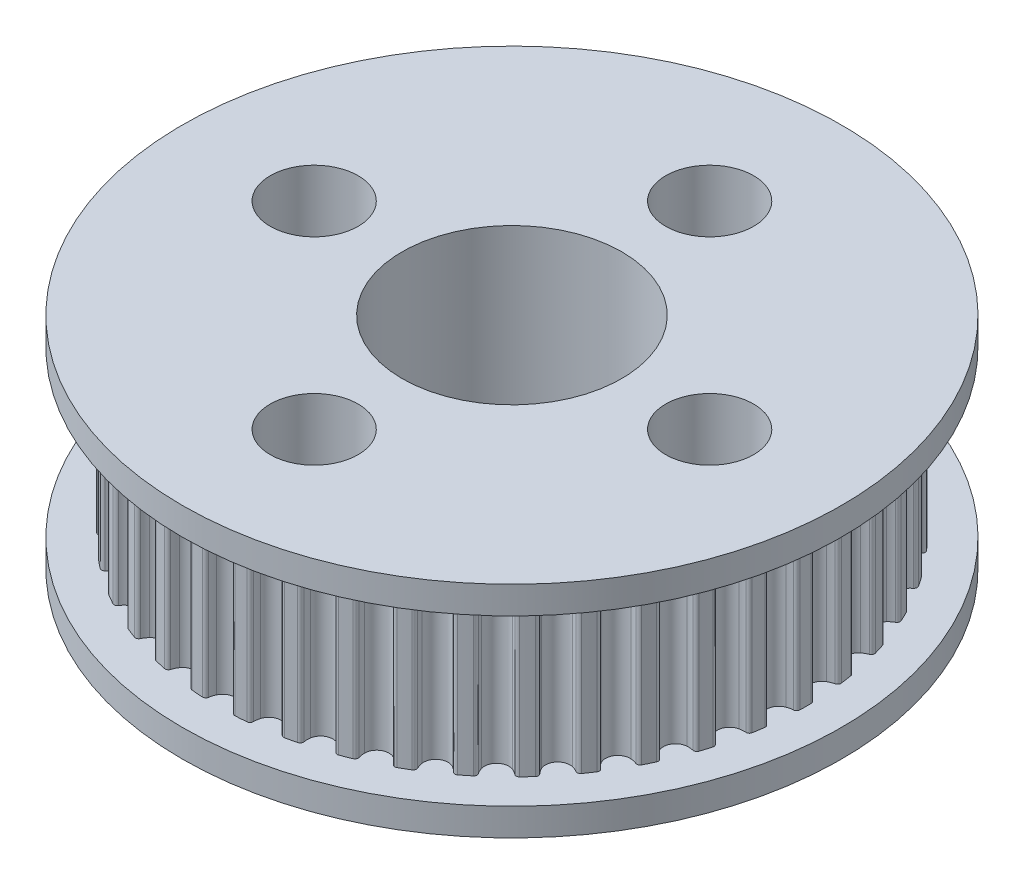
SolidWorks part; units mm, degrees
ref_plane "Front Plane" through (0, 0, 0) normal (0, 0, 1) x (1, 0, 0)
ref_plane "Top Plane" through (0, 0, 0) normal (0, 1, 0) x (1, 0, 0)
ref_plane "Right Plane" through (0, 0, 0) normal (1, 0, 0) x (0, 0, -1)
sketch "Sketch2" plane through (0, 0, 0) normal (0, 1, 0) x (1, 0, 0)
  arc A0 (-0.7447, 13.3442) -> (0.7447, 13.3442) centre (0, 0) ccw
  arc A1 (-0.5031, 12.9334) -> (0.5031, 12.9334) centre (0, 13.17) ccw
  arc A2 (0.5031, 12.9334) -> (0.5879, 13.2159) centre (-0.4018, 13.359) ccw
  arc A3 (-0.5879, 13.2159) -> (-0.5031, 12.9334) centre (0.4018, 13.359) ccw
  arc A4 (-0.7447, 13.3442) -> (-0.5879, 13.2159) centre (-0.7364, 13.1945) cw
  arc A5 (0.7447, 13.3442) -> (0.5879, 13.2159) centre (0.7364, 13.1945) ccw
  arc A6 (1.2524, 13.3062) -> (1.3884, 13.1559) centre (1.2384, 13.1568) cw
  arc A7 (1.3884, 13.1559) -> (1.4301, 12.8639) centre (2.3883, 13.1499) ccw
  arc A8 (1.4301, 12.8639) -> (2.4251, 12.7139) centre (1.9629, 13.0229) ccw
  arc A9 (2.4251, 12.7139) -> (2.5511, 12.9807) centre (1.5938, 13.2696) ccw
  arc A10 (2.7253, 13.0842) -> (2.5511, 12.9807) centre (2.6947, 12.9373) ccw
  arc A11 (3.2216, 12.9709) -> (3.3336, 12.8021) centre (3.1855, 12.8253) cw
  arc A12 (3.3336, 12.8021) -> (3.3314, 12.5071) centre (4.3216, 12.647) ccw
  arc A13 (3.3314, 12.5071) -> (4.293, 12.2105) centre (3.8819, 12.5849) ccw
  arc A14 (4.293, 12.2105) -> (4.4573, 12.4555) centre (3.5537, 12.8839) ccw
  arc A15 (4.6449, 12.5319) -> (4.4573, 12.4555) centre (4.5928, 12.3912) ccw
  arc A16 (5.1188, 12.3459) -> (5.2045, 12.1622) centre (5.0614, 12.2073) cw
  arc A17 (5.2045, 12.1622) -> (5.1583, 11.8709) centre (6.1582, 11.8617) ccw
  arc A18 (5.1583, 11.8709) -> (6.0649, 11.4343) centre (5.7142, 11.8658) ccw
  arc A19 (6.0649, 11.4343) -> (6.2639, 11.652) centre (5.4342, 12.2103) ccw
  arc A20 (6.4608, 11.6996) -> (6.2639, 11.652) centre (6.3883, 11.5683) ccw
  arc A21 (6.9017, 11.4451) -> (6.959, 11.2507) centre (6.8243, 11.3166) cw
  arc A22 (6.959, 11.2507) -> (6.8699, 10.9695) centre (7.8573, 10.8114) ccw
  arc A23 (6.8699, 10.9695) -> (7.7013, 10.4026) centre (7.4189, 10.8816) ccw
  arc A24 (7.7013, 10.4026) -> (7.9306, 10.5883) centre (7.1934, 11.264) ccw
  arc A25 (8.1324, 10.606) -> (7.9306, 10.5883) centre (8.0411, 10.487) ccw
  arc A26 (8.5304, 10.2886) -> (8.5581, 10.0879) centre (8.4347, 10.1731) cw
  arc A27 (8.5581, 10.0879) -> (8.4281, 9.8231) centre (9.3809, 9.5195) ccw
  arc A28 (8.4281, 9.8231) -> (9.1658, 9.1386) centre (8.9579, 9.6543) ccw
  arc A29 (9.1658, 9.1386) -> (9.4201, 9.2881) centre (8.7919, 10.0661) ccw
  arc A30 (9.6223, 9.2755) -> (9.4201, 9.2881) centre (9.5143, 9.1714) ccw
  arc A31 (9.9686, 8.9023) -> (9.9661, 8.6997) centre (9.8567, 8.8023) cw
  arc A32 (9.9661, 8.6997) -> (9.798, 8.4572) centre (10.695, 8.015) ccw
  arc A33 (9.798, 8.4572) -> (10.4254, 7.6705) centre (10.2967, 8.2114) ccw
  arc A34 (10.4254, 7.6705) -> (10.6992, 7.7803) centre (10.1939, 8.6433) ccw
  arc A35 (10.8973, 7.7377) -> (10.6992, 7.7803) centre (10.775, 7.6509) ccw
  arc A36 (11.1841, 7.3171) -> (11.1514, 7.1171) centre (11.0585, 7.235) cw
  arc A37 (11.1514, 7.1171) -> (10.9491, 6.9024) centre (11.7701, 6.3315) ccw
  arc A38 (10.9491, 6.9024) -> (11.4522, 6.031) centre (11.4056, 6.585) ccw
  arc A39 (11.4522, 6.031) -> (11.7393, 6.0988) centre (11.3683, 7.0274) ccw
  arc A40 (11.9288, 6.0271) -> (11.7393, 6.0988) centre (11.7949, 5.9595) ccw
  arc A41 (12.1497, 5.5685) -> (12.0876, 5.3756) centre (12.0133, 5.506) cw
  arc A42 (12.0876, 5.3756) -> (11.8555, 5.1934) centre (12.5823, 4.5066) ccw
  arc A43 (11.8555, 5.1934) -> (12.2232, 4.2567) centre (12.2596, 4.8115) ccw
  arc A44 (12.2232, 4.2567) -> (12.5172, 4.281) centre (12.2887, 5.2546) ccw
  arc A45 (12.6939, 4.1819) -> (12.5172, 4.281) centre (12.5514, 4.135) ccw
  arc A46 (12.8439, 3.6954) -> (12.7537, 3.514) centre (12.6998, 3.654) cw
  arc A47 (12.7537, 3.514) -> (12.4972, 3.3685) centre (13.1134, 2.5809) ccw
  arc A48 (12.4972, 3.3685) -> (12.7211, 2.3874) centre (12.8398, 2.9306) ccw
  arc A49 (12.7211, 2.3874) -> (13.0154, 2.3676) centre (12.9346, 3.3644) ccw
  arc A50 (13.1754, 2.2433) -> (13.0154, 2.3676) centre (13.0275, 2.2181) ccw
  arc A51 (13.2513, 1.7399) -> (13.135, 1.5739) centre (13.1025, 1.7204) cw
  arc A52 (13.135, 1.5739) -> (12.8596, 1.4682) centre (13.3516, 0.5977) ccw
  arc A53 (12.8596, 1.4682) -> (12.9348, 0.4648) centre (13.1332, 0.9842) ccw
  arc A54 (12.9348, 0.4648) -> (13.2229, 0.4013) centre (13.2916, 1.399) ccw
  arc A55 (13.3626, 0.2545) -> (13.2229, 0.4013) centre (13.2126, 0.2517) ccw
  arc A56 (13.3626, -0.2545) -> (13.2229, -0.4013) centre (13.2126, -0.2517) cw
  arc A57 (13.2229, -0.4013) -> (12.9348, -0.4648) centre (13.2916, -1.399) ccw
  arc A58 (12.9348, -0.4648) -> (12.8596, -1.4682) centre (13.1332, -0.9842) ccw
  arc A59 (12.8596, -1.4682) -> (13.135, -1.5739) centre (13.3516, -0.5977) ccw
  arc A60 (13.2513, -1.7399) -> (13.135, -1.5739) centre (13.1025, -1.7204) ccw
  arc A61 (13.1754, -2.2433) -> (13.0154, -2.3676) centre (13.0275, -2.2181) cw
  arc A62 (13.0154, -2.3676) -> (12.7211, -2.3874) centre (12.9346, -3.3644) ccw
  arc A63 (12.7211, -2.3874) -> (12.4972, -3.3685) centre (12.8398, -2.9306) ccw
  arc A64 (12.4972, -3.3685) -> (12.7537, -3.514) centre (13.1134, -2.5809) ccw
  arc A65 (12.8439, -3.6954) -> (12.7537, -3.514) centre (12.6998, -3.654) ccw
  arc A66 (12.6939, -4.1819) -> (12.5172, -4.281) centre (12.5514, -4.135) cw
  arc A67 (12.5172, -4.281) -> (12.2232, -4.2567) centre (12.2887, -5.2546) ccw
  arc A68 (12.2232, -4.2567) -> (11.8555, -5.1934) centre (12.2596, -4.8115) ccw
  arc A69 (11.8555, -5.1934) -> (12.0876, -5.3756) centre (12.5823, -4.5066) ccw
  arc A70 (12.1497, -5.5685) -> (12.0876, -5.3756) centre (12.0133, -5.506) ccw
  arc A71 (11.9288, -6.0271) -> (11.7393, -6.0988) centre (11.7949, -5.9595) cw
  arc A72 (11.7393, -6.0988) -> (11.4522, -6.031) centre (11.3683, -7.0274) ccw
  arc A73 (11.4522, -6.031) -> (10.9491, -6.9024) centre (11.4056, -6.585) ccw
  arc A74 (10.9491, -6.9024) -> (11.1514, -7.1171) centre (11.7701, -6.3315) ccw
  arc A75 (11.1841, -7.3171) -> (11.1514, -7.1171) centre (11.0585, -7.235) ccw
  arc A76 (10.8973, -7.7377) -> (10.6992, -7.7803) centre (10.775, -7.6509) cw
  arc A77 (10.6992, -7.7803) -> (10.4254, -7.6705) centre (10.1939, -8.6433) ccw
  arc A78 (10.4254, -7.6705) -> (9.798, -8.4572) centre (10.2967, -8.2114) ccw
  arc A79 (9.798, -8.4572) -> (9.9661, -8.6997) centre (10.695, -8.015) ccw
  arc A80 (9.9686, -8.9023) -> (9.9661, -8.6997) centre (9.8567, -8.8023) ccw
  arc A81 (9.6223, -9.2755) -> (9.4201, -9.2881) centre (9.5143, -9.1714) cw
  arc A82 (9.4201, -9.2881) -> (9.1658, -9.1386) centre (8.7919, -10.0661) ccw
  arc A83 (9.1658, -9.1386) -> (8.4281, -9.8231) centre (8.9579, -9.6543) ccw
  arc A84 (8.4281, -9.8231) -> (8.5581, -10.0879) centre (9.3809, -9.5195) ccw
  arc A85 (8.5304, -10.2886) -> (8.5581, -10.0879) centre (8.4347, -10.1731) ccw
  arc A86 (8.1324, -10.606) -> (7.9306, -10.5883) centre (8.0411, -10.487) cw
  arc A87 (7.9306, -10.5883) -> (7.7013, -10.4026) centre (7.1934, -11.264) ccw
  arc A88 (7.7013, -10.4026) -> (6.8699, -10.9695) centre (7.4189, -10.8816) ccw
  arc A89 (6.8699, -10.9695) -> (6.959, -11.2507) centre (7.8573, -10.8114) ccw
  arc A90 (6.9017, -11.4451) -> (6.959, -11.2507) centre (6.8243, -11.3166) ccw
  arc A91 (6.4608, -11.6996) -> (6.2639, -11.652) centre (6.3883, -11.5683) cw
  arc A92 (6.2639, -11.652) -> (6.0649, -11.4343) centre (5.4342, -12.2103) ccw
  arc A93 (6.0649, -11.4343) -> (5.1583, -11.8709) centre (5.7142, -11.8658) ccw
  arc A94 (5.1583, -11.8709) -> (5.2045, -12.1622) centre (6.1582, -11.8617) ccw
  arc A95 (5.1188, -12.3459) -> (5.2045, -12.1622) centre (5.0614, -12.2073) ccw
  arc A96 (4.6449, -12.5319) -> (4.4573, -12.4555) centre (4.5928, -12.3912) cw
  arc A97 (4.4573, -12.4555) -> (4.293, -12.2105) centre (3.5537, -12.8839) ccw
  arc A98 (4.293, -12.2105) -> (3.3314, -12.5071) centre (3.8819, -12.5849) ccw
  arc A99 (3.3314, -12.5071) -> (3.3336, -12.8021) centre (4.3216, -12.647) ccw
  arc A100 (3.2216, -12.9709) -> (3.3336, -12.8021) centre (3.1855, -12.8253) ccw
  arc A101 (2.7253, -13.0842) -> (2.5511, -12.9807) centre (2.6947, -12.9373) cw
  arc A102 (2.5511, -12.9807) -> (2.4251, -12.7139) centre (1.5938, -13.2696) ccw
  arc A103 (2.4251, -12.7139) -> (1.4301, -12.8639) centre (1.9629, -13.0229) ccw
  arc A104 (1.4301, -12.8639) -> (1.3884, -13.1559) centre (2.3883, -13.1499) ccw
  arc A105 (1.2524, -13.3062) -> (1.3884, -13.1559) centre (1.2384, -13.1568) ccw
  arc A106 (0.7447, -13.3442) -> (0.5879, -13.2159) centre (0.7364, -13.1945) cw
  arc A107 (0.5879, -13.2159) -> (0.5031, -12.9334) centre (-0.4018, -13.359) ccw
  arc A108 (0.5031, -12.9334) -> (-0.5031, -12.9334) centre (0, -13.17) ccw
  arc A109 (-0.5031, -12.9334) -> (-0.5879, -13.2159) centre (0.4018, -13.359) ccw
  arc A110 (-0.7447, -13.3442) -> (-0.5879, -13.2159) centre (-0.7364, -13.1945) ccw
  arc A111 (-1.2524, -13.3062) -> (-1.3884, -13.1559) centre (-1.2384, -13.1568) cw
  arc A112 (-1.3884, -13.1559) -> (-1.4301, -12.8639) centre (-2.3883, -13.1499) ccw
  arc A113 (-1.4301, -12.8639) -> (-2.4251, -12.7139) centre (-1.9629, -13.0229) ccw
  arc A114 (-2.4251, -12.7139) -> (-2.5511, -12.9807) centre (-1.5938, -13.2696) ccw
  arc A115 (-2.7253, -13.0842) -> (-2.5511, -12.9807) centre (-2.6947, -12.9373) ccw
  arc A116 (-3.2216, -12.9709) -> (-3.3336, -12.8021) centre (-3.1855, -12.8253) cw
  arc A117 (-3.3336, -12.8021) -> (-3.3314, -12.5071) centre (-4.3216, -12.647) ccw
  arc A118 (-3.3314, -12.5071) -> (-4.293, -12.2105) centre (-3.8819, -12.5849) ccw
  arc A119 (-4.293, -12.2105) -> (-4.4573, -12.4555) centre (-3.5537, -12.8839) ccw
  arc A120 (-4.6449, -12.5319) -> (-4.4573, -12.4555) centre (-4.5928, -12.3912) ccw
  arc A121 (-5.1188, -12.3459) -> (-5.2045, -12.1622) centre (-5.0614, -12.2073) cw
  arc A122 (-5.2045, -12.1622) -> (-5.1583, -11.8709) centre (-6.1582, -11.8617) ccw
  arc A123 (-5.1583, -11.8709) -> (-6.0649, -11.4343) centre (-5.7142, -11.8658) ccw
  arc A124 (-6.0649, -11.4343) -> (-6.2639, -11.652) centre (-5.4342, -12.2103) ccw
  arc A125 (-6.4608, -11.6996) -> (-6.2639, -11.652) centre (-6.3883, -11.5683) ccw
  arc A126 (-6.9017, -11.4451) -> (-6.959, -11.2507) centre (-6.8243, -11.3166) cw
  arc A127 (-6.959, -11.2507) -> (-6.8699, -10.9695) centre (-7.8573, -10.8114) ccw
  arc A128 (-6.8699, -10.9695) -> (-7.7013, -10.4026) centre (-7.4189, -10.8816) ccw
  arc A129 (-7.7013, -10.4026) -> (-7.9306, -10.5883) centre (-7.1934, -11.264) ccw
  arc A130 (-8.1324, -10.606) -> (-7.9306, -10.5883) centre (-8.0411, -10.487) ccw
  arc A131 (-8.5304, -10.2886) -> (-8.5581, -10.0879) centre (-8.4347, -10.1731) cw
  arc A132 (-8.5581, -10.0879) -> (-8.4281, -9.8231) centre (-9.3809, -9.5195) ccw
  arc A133 (-8.4281, -9.8231) -> (-9.1658, -9.1386) centre (-8.9579, -9.6543) ccw
  arc A134 (-9.1658, -9.1386) -> (-9.4201, -9.2881) centre (-8.7919, -10.0661) ccw
  arc A135 (-9.6223, -9.2755) -> (-9.4201, -9.2881) centre (-9.5143, -9.1714) ccw
  arc A136 (-9.9686, -8.9023) -> (-9.9661, -8.6997) centre (-9.8567, -8.8023) cw
  arc A137 (-9.9661, -8.6997) -> (-9.798, -8.4572) centre (-10.695, -8.015) ccw
  arc A138 (-9.798, -8.4572) -> (-10.4254, -7.6705) centre (-10.2967, -8.2114) ccw
  arc A139 (-10.4254, -7.6705) -> (-10.6992, -7.7803) centre (-10.1939, -8.6433) ccw
  arc A140 (-10.8973, -7.7377) -> (-10.6992, -7.7803) centre (-10.775, -7.6509) ccw
  arc A141 (-11.1841, -7.3171) -> (-11.1514, -7.1171) centre (-11.0585, -7.235) cw
  arc A142 (-11.1514, -7.1171) -> (-10.9491, -6.9024) centre (-11.7701, -6.3315) ccw
  arc A143 (-10.9491, -6.9024) -> (-11.4522, -6.031) centre (-11.4056, -6.585) ccw
  arc A144 (-11.4522, -6.031) -> (-11.7393, -6.0988) centre (-11.3683, -7.0274) ccw
  arc A145 (-11.9288, -6.0271) -> (-11.7393, -6.0988) centre (-11.7949, -5.9595) ccw
  arc A146 (-12.1497, -5.5685) -> (-12.0876, -5.3756) centre (-12.0133, -5.506) cw
  arc A147 (-12.0876, -5.3756) -> (-11.8555, -5.1934) centre (-12.5823, -4.5066) ccw
  arc A148 (-11.8555, -5.1934) -> (-12.2232, -4.2567) centre (-12.2596, -4.8115) ccw
  arc A149 (-12.2232, -4.2567) -> (-12.5172, -4.281) centre (-12.2887, -5.2546) ccw
  arc A150 (-12.6939, -4.1819) -> (-12.5172, -4.281) centre (-12.5514, -4.135) ccw
  arc A151 (-12.8439, -3.6954) -> (-12.7537, -3.514) centre (-12.6998, -3.654) cw
  arc A152 (-12.7537, -3.514) -> (-12.4972, -3.3685) centre (-13.1134, -2.5809) ccw
  arc A153 (-12.4972, -3.3685) -> (-12.7211, -2.3874) centre (-12.8398, -2.9306) ccw
  arc A154 (-12.7211, -2.3874) -> (-13.0154, -2.3676) centre (-12.9346, -3.3644) ccw
  arc A155 (-13.1754, -2.2433) -> (-13.0154, -2.3676) centre (-13.0275, -2.2181) ccw
  arc A156 (-13.2513, -1.7399) -> (-13.135, -1.5739) centre (-13.1025, -1.7204) cw
  arc A157 (-13.135, -1.5739) -> (-12.8596, -1.4682) centre (-13.3516, -0.5977) ccw
  arc A158 (-12.8596, -1.4682) -> (-12.9348, -0.4648) centre (-13.1332, -0.9842) ccw
  arc A159 (-12.9348, -0.4648) -> (-13.2229, -0.4013) centre (-13.2916, -1.399) ccw
  arc A160 (-13.3626, -0.2545) -> (-13.2229, -0.4013) centre (-13.2126, -0.2517) ccw
  arc A161 (-13.3626, 0.2545) -> (-13.2229, 0.4013) centre (-13.2126, 0.2517) cw
  arc A162 (-13.2229, 0.4013) -> (-12.9348, 0.4648) centre (-13.2916, 1.399) ccw
  arc A163 (-12.9348, 0.4648) -> (-12.8596, 1.4682) centre (-13.1332, 0.9842) ccw
  arc A164 (-12.8596, 1.4682) -> (-13.135, 1.5739) centre (-13.3516, 0.5977) ccw
  arc A165 (-13.2513, 1.7399) -> (-13.135, 1.5739) centre (-13.1025, 1.7204) ccw
  arc A166 (-13.1754, 2.2433) -> (-13.0154, 2.3676) centre (-13.0275, 2.2181) cw
  arc A167 (-13.0154, 2.3676) -> (-12.7211, 2.3874) centre (-12.9346, 3.3644) ccw
  arc A168 (-12.7211, 2.3874) -> (-12.4972, 3.3685) centre (-12.8398, 2.9306) ccw
  arc A169 (-12.4972, 3.3685) -> (-12.7537, 3.514) centre (-13.1134, 2.5809) ccw
  arc A170 (-12.8439, 3.6954) -> (-12.7537, 3.514) centre (-12.6998, 3.654) ccw
  arc A171 (-12.6939, 4.1819) -> (-12.5172, 4.281) centre (-12.5514, 4.135) cw
  arc A172 (-12.5172, 4.281) -> (-12.2232, 4.2567) centre (-12.2887, 5.2546) ccw
  arc A173 (-12.2232, 4.2567) -> (-11.8555, 5.1934) centre (-12.2596, 4.8115) ccw
  arc A174 (-11.8555, 5.1934) -> (-12.0876, 5.3756) centre (-12.5823, 4.5066) ccw
  arc A175 (-12.1497, 5.5685) -> (-12.0876, 5.3756) centre (-12.0133, 5.506) ccw
  arc A176 (-11.9288, 6.0271) -> (-11.7393, 6.0988) centre (-11.7949, 5.9595) cw
  arc A177 (-11.7393, 6.0988) -> (-11.4522, 6.031) centre (-11.3683, 7.0274) ccw
  arc A178 (-11.4522, 6.031) -> (-10.9491, 6.9024) centre (-11.4056, 6.585) ccw
  arc A179 (-10.9491, 6.9024) -> (-11.1514, 7.1171) centre (-11.7701, 6.3315) ccw
  arc A180 (-11.1841, 7.3171) -> (-11.1514, 7.1171) centre (-11.0585, 7.235) ccw
  arc A181 (-10.8973, 7.7377) -> (-10.6992, 7.7803) centre (-10.775, 7.6509) cw
  arc A182 (-10.6992, 7.7803) -> (-10.4254, 7.6705) centre (-10.1939, 8.6433) ccw
  arc A183 (-10.4254, 7.6705) -> (-9.798, 8.4572) centre (-10.2967, 8.2114) ccw
  arc A184 (-9.798, 8.4572) -> (-9.9661, 8.6997) centre (-10.695, 8.015) ccw
  arc A185 (-9.9686, 8.9023) -> (-9.9661, 8.6997) centre (-9.8567, 8.8023) ccw
  arc A186 (-9.6223, 9.2755) -> (-9.4201, 9.2881) centre (-9.5143, 9.1714) cw
  arc A187 (-9.4201, 9.2881) -> (-9.1658, 9.1386) centre (-8.7919, 10.0661) ccw
  arc A188 (-9.1658, 9.1386) -> (-8.4281, 9.8231) centre (-8.9579, 9.6543) ccw
  arc A189 (-8.4281, 9.8231) -> (-8.5581, 10.0879) centre (-9.3809, 9.5195) ccw
  arc A190 (-8.5304, 10.2886) -> (-8.5581, 10.0879) centre (-8.4347, 10.1731) ccw
  arc A191 (-8.1324, 10.606) -> (-7.9306, 10.5883) centre (-8.0411, 10.487) cw
  arc A192 (-7.9306, 10.5883) -> (-7.7013, 10.4026) centre (-7.1934, 11.264) ccw
  arc A193 (-7.7013, 10.4026) -> (-6.8699, 10.9695) centre (-7.4189, 10.8816) ccw
  arc A194 (-6.8699, 10.9695) -> (-6.959, 11.2507) centre (-7.8573, 10.8114) ccw
  arc A195 (-6.9017, 11.4451) -> (-6.959, 11.2507) centre (-6.8243, 11.3166) ccw
  arc A196 (-6.4608, 11.6996) -> (-6.2639, 11.652) centre (-6.3883, 11.5683) cw
  arc A197 (-6.2639, 11.652) -> (-6.0649, 11.4343) centre (-5.4342, 12.2103) ccw
  arc A198 (-6.0649, 11.4343) -> (-5.1583, 11.8709) centre (-5.7142, 11.8658) ccw
  arc A199 (-5.1583, 11.8709) -> (-5.2045, 12.1622) centre (-6.1582, 11.8617) ccw
  arc A200 (-5.1188, 12.3459) -> (-5.2045, 12.1622) centre (-5.0614, 12.2073) ccw
  arc A201 (-4.6449, 12.5319) -> (-4.4573, 12.4555) centre (-4.5928, 12.3912) cw
  arc A202 (-4.4573, 12.4555) -> (-4.293, 12.2105) centre (-3.5537, 12.8839) ccw
  arc A203 (-4.293, 12.2105) -> (-3.3314, 12.5071) centre (-3.8819, 12.5849) ccw
  arc A204 (-3.3314, 12.5071) -> (-3.3336, 12.8021) centre (-4.3216, 12.647) ccw
  arc A205 (-3.2216, 12.9709) -> (-3.3336, 12.8021) centre (-3.1855, 12.8253) ccw
  arc A206 (-2.7253, 13.0842) -> (-2.5511, 12.9807) centre (-2.6947, 12.9373) cw
  arc A207 (-2.5511, 12.9807) -> (-2.4251, 12.7139) centre (-1.5938, 13.2696) ccw
  arc A208 (-2.4251, 12.7139) -> (-1.4301, 12.8639) centre (-1.9629, 13.0229) ccw
  arc A209 (-1.4301, 12.8639) -> (-1.3884, 13.1559) centre (-2.3883, 13.1499) ccw
  arc A210 (-1.2524, 13.3062) -> (-1.3884, 13.1559) centre (-1.2384, 13.1568) ccw
  point P5 (0, 13.365)
  point P468 (0, 0)
  dimension "D1" = 26.73
  dimension "D2" = 1.112
  dimension "D4" = 2
  dimension "D5" = 2
  dimension "D6" = 0.15
  dimension "D3" = 0.195
  dimension "D7" = 42
extrude "Boss-Extrude1" add sketch "Sketch2" along normal mid plane 10 contours A0 A210 A209 A208 A207 A206 A205 A204 A203 A202 A201 A200 A199 A198 A197 A196 A195 A194 A193 A192 A191 A190 A189 A188 A187 A186 A185 A184 A183 A182 A181 A180 A179 A178 A177 A176 A175 A174 A173 A172 A171 A170 A169 region at (0, 0, 0)
sketch "Sketch3" plane through (0, 5, 0) normal (0, 1, 0) x (1, 0, 0)
  circle A0 centre (0, 0) radius 15
  dimension "D1" = 30
extrude "Boss-Extrude2" add sketch "Sketch3" against normal blind 1.25
mirror "Mirror1" about plane through (0, 0, 0) normal (0, 1, 0) of "Boss-Extrude2"
sketch "Sketch4" plane through (0, 5, 0) normal (0, 1, 0) x (1, 0, 0)
  circle A0 centre (0, 0) radius 9
  circle A1 centre (0, 9) radius 2
  circle A2 centre (9, 0) radius 2
  circle A3 centre (0, -9) radius 2
  circle A4 centre (-9, 0) radius 2
  circle A5 centre (0, 0) radius 5
  dimension "D1" = 18
  dimension "D2" = 4
  dimension "D3" = 4
  dimension "D4" = 4
  dimension "D5" = 4
  dimension "D6" = 10
extrude "Cut-Extrude1" cut sketch "Sketch4" against normal through all contours A0 A4 | A0 A4 | A0 A1 | A0 A1 | A5 | A0 A2 | A0 A2 | A0 A3 | A0 A3 region at (8.1124, 5, 0) region at (9.8075, 5, 0) region at (0, 5, -8.1124) region at (0, 5, -9.8075) region at (0, 5, 9.8075) region at (0, 5, 8.1124) region at (-8.1124, 5, 0) region at (-9.8075, 5, 0) region at (0, 5, 0)
sketch "Sketch5" plane through (0, -5, 0) normal (0, -1, 0) x (1, 0, 0)
  circle A0 centre (0, 9) radius 3.5
  circle A1 centre (9, 0) radius 3.5
  circle A2 centre (0, -9) radius 3.5
  circle A3 centre (-9, 0) radius 3.5
  dimension "D1" = 7
  dimension "D2" = 7
  dimension "D3" = 7
  dimension "D4" = 7
extrude "Cut-Extrude2" cut sketch "Sketch5" against normal blind 2
